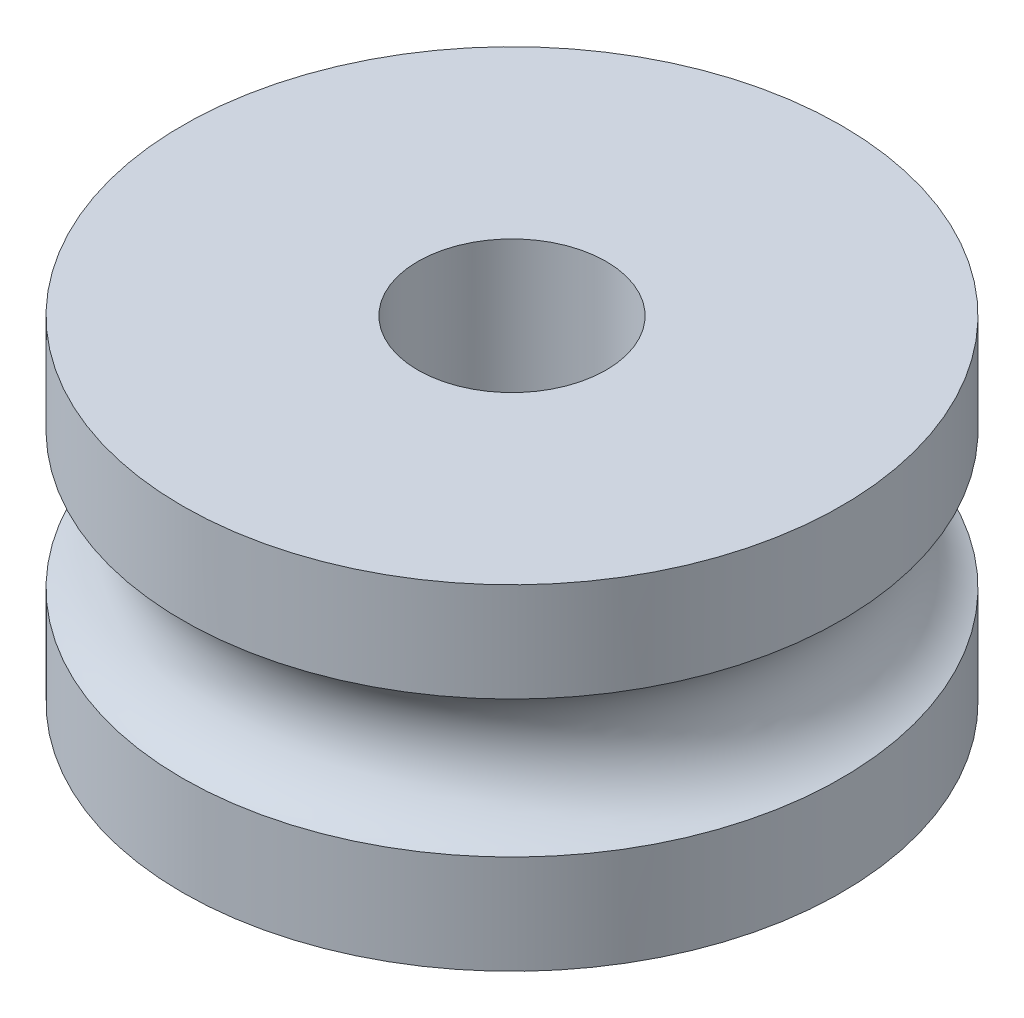
SolidWorks part; units mm, degrees
ref_plane "Front Plane" through (0, 0, 0) normal (0, 0, 1) x (1, 0, 0)
ref_plane "Top Plane" through (0, 0, 0) normal (0, 1, 0) x (1, 0, 0)
ref_plane "Right Plane" through (0, 0, 0) normal (1, 0, 0) x (0, 0, -1)
sketch "Sketch1" plane through (0, 0, 0) normal (0, 1, 0) x (1, 0, 0)
  circle A0 centre (0, 0) radius 7.875
  circle A1 centre (0, 0) radius 2.25
  dimension "D1" = 15.75
  dimension "D2" = 4.5
extrude "Boss-Extrude1" add sketch "Sketch1" along normal blind 8
sketch "Sketch2" plane through (0, 8, 0) normal (0, 1, 0) x (1, 0, 0)
  circle A0 centre (0, 0) radius 4
  circle A1 centre (0, 0) radius 2.25 construction
  dimension "D1" = 8
extrude "Cut-Extrude1" [suppressed] cut sketch "Sketch2" against normal blind 3 draft 45
sketch "Sketch3" plane through (0, 0, 0) normal (0, -1, 0) x (-1, 0, 0)
  circle A0 centre (0, 0) radius 4
  circle A1 centre (0, 0) radius 2.25 construction
  dimension "D1" = 8
extrude "Cut-Extrude2" cut sketch "Sketch3" against normal blind 3
sketch "Sketch4" plane through (0, 3, 0) normal (0, -1, 0) x (1, 0, 0)
  circle A0 centre (0, 0) radius 2.5
  circle A1 centre (0, 0) radius 4
  circle A2 centre (0, 0) radius 4 construction
  dimension "D1" = 5
extrude "Boss-Extrude2" [suppressed] add sketch "Sketch4" along normal blind 2
sketch "Sketch5" [suppressed] plane through (0, 8, 0) normal (0, 1, 0) x (1, 0, 0)
  line L0 (4.437, 6.506) -> (4.437, -6.506)
  line L1 (3.937, -6.9653) -> (3.937, 4.6059) construction
  circle A0 centre (0, 0) radius 7.875 construction
  arc A1 (4.437, -6.506) -> (4.437, 6.506) centre (0, 0) ccw
  dimension "D1" = 0.5
extrude "Boss-Extrude3" [suppressed] add sketch "Sketch5" along normal blind 8
sketch "Sketch6" [suppressed] plane through (3.937, 0, 0) normal (1, 0, 0) x (0, 0, -1)
  line L0 (14.052, 7.7042) -> (-6.463, 7.7042) construction
  line L1 (-6.506, 16) -> (-3.506, 16)
  line L2 (-6.506, 16) -> (-6.506, 7.7042)
  line L3 (-6.506, 7.7042) -> (-3.506, 7.7042)
  line L4 (-3.506, 16) -> (-3.506, 7.7042)
  line L5 (0, 16) -> (0, 7.7042) construction
  line L6 (6.506, 16) -> (-6.506, 16) construction
  line L7 (3.506, 16) -> (3.506, 7.7042)
  line L8 (6.506, 7.7042) -> (3.506, 7.7042)
  line L9 (6.506, 16) -> (6.506, 7.7042)
  line L10 (6.506, 16) -> (3.506, 16)
  dimension "D1" = 3
extrude "Cut-Extrude3" [suppressed] cut sketch "Sketch6" along normal through all
sketch "Sketch7" plane through (0, 8, 0) normal (0, 1, 0) x (1, 0, 0)
  circle A0 centre (0, 0) radius 1.25
  circle A1 centre (0, 0) radius 2.5
  dimension "D1" = 2.5
  dimension "D2" = 5
extrude "Boss-Extrude4" [suppressed] add sketch "Sketch7" along normal blind 10 separate body
sketch "Sketch9" plane through (11.2113, 0, 0) normal (1, 0, 0) x (0, 0, -1)
  circle A0 centre (-6.463, 18.7042) radius 6.35
  circle A1 centre (-6.463, 18.7042) radius 6.35 construction
extrude "Cut-Extrude4" [suppressed] cut sketch "Sketch9" against normal through all
sketch "Sketch10" plane through (6.1024, 0, 0) normal (1, 0, 0) x (0, 0, -1)
  circle A0 centre (8.6773, 18.7042) radius 8.5
  dimension "D1" = 17
extrude "Cut-Extrude5" [suppressed] cut sketch "Sketch10" against normal through all
ref_plane "Plane1" [suppressed] through (2.5, 0, 0) normal (1, 0, 0) x (0, 0, -1)
sketch "Sketch11" plane through (0, 0, 0) normal (0, 0, 1) x (1, 0, 0)
  line L1 (7.875, 8) -> (-7.875, 8) construction
  line L2 (0, 0) -> (0, 7.6573) construction
  circle A0 centre (-8.5, 4) radius 1.75
  point P9 (0, 0)
  dimension "D1" = 3.5
  dimension "D2" = 4
  dimension "D3" = 8.5
revolve "Cut-Revolve1" cut sketch "Sketch11" angle 360 about L2
